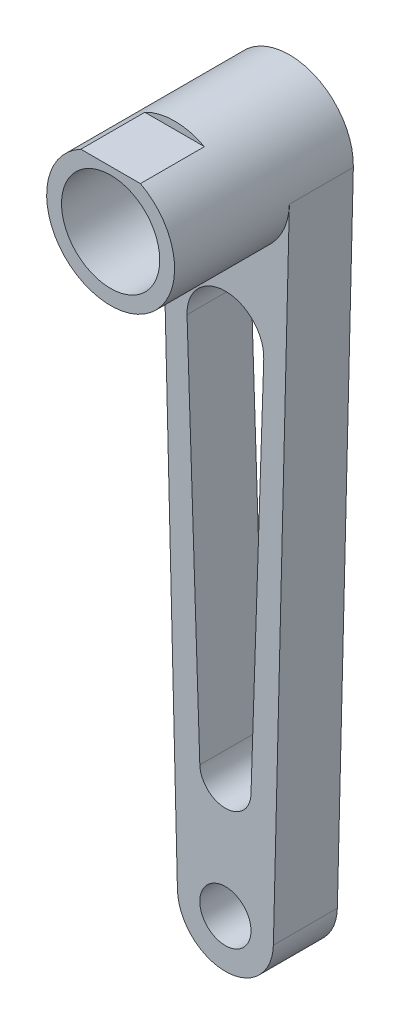
SolidWorks part; units mm, degrees
material "PEI"
ref_plane "Front Plane" through (0, 0, 0) normal (0, 0, 1) x (1, 0, 0)
ref_plane "Top Plane" through (0, 0, 0) normal (0, 1, 0) x (1, 0, 0)
ref_plane "Right Plane" through (0, 0, 0) normal (1, 0, 0) x (0, 0, -1)
sketch "Sketch1" plane through (0, 0, 0) normal (0, 0, 1) x (1, 0, 0)
  line L0 (-10.294, 11.8201) -> (-7.347, -107.9077)
  line L1 (0, -101.6) -> (0, 0) construction
  line L2 (7.347, -107.9067) -> (10.2653, 10.6574)
  line L3 (6.244, -15.7837) -> (3.867, -87.0546)
  line L4 (-6.2592, -15.3276) -> (-3.8401, -87.8596)
  circle A0 centre (0, 0) radius 10
  circle A1 centre (0, 0) radius 7.675
  circle A2 centre (0, -101.6) radius 7.5
  circle A3 centre (0, -101.6) radius 4
  circle A6 centre (0, -23) radius 6
  circle A7 centre (0, -83) radius 4
  dimension "D1" = 15.35
  dimension "D2" = 20
  dimension "D3" = 15
  dimension "D5" = 8
  dimension "D7" = 12
  dimension "D8" = 60
  dimension "D9" = 23
  dimension "D6" = 8
  dimension "D4" = 101.6
extrude "Boss-Extrude2" add sketch "Sketch1" along normal blind 10 contours L1 A2 L2 A0 | A2 L1 A0 L0 | A3 A2 region at (0, -11.0349, 0) region at (-0.0897, -94.3127, 0)
extrude "Boss-Extrude3" add sketch "Sketch1<6>" along normal blind 27.94 contours A0 A1 region at (-0.1196, 9.7164, 0)
sketch "Sketch1<6>" plane through (0, 0, 0) normal (0, 0, 1) x (1, 0, 0) same geometry as "Sketch1"
sketch "Sketch2" plane through (0, 0, 27.94) normal (0, 0, 1) x (1, 0, 0)
  line L0 (-10.0333, 8.85) -> (9.9921, 8.85)
  line L1 (9.9921, 8.85) -> (9.9921, 18.6582)
  line L2 (9.9921, 18.6582) -> (-10.0333, 18.6582)
  line L3 (-10.0333, 18.6582) -> (-10.0333, 8.85)
  circle A0 centre (0, 0) radius 10 construction
  point P3 (-0.0206, 8.85)
  dimension "D1" = 8.85
extrude "Cut-Extrude1" cut sketch "Sketch2" against normal blind 10
